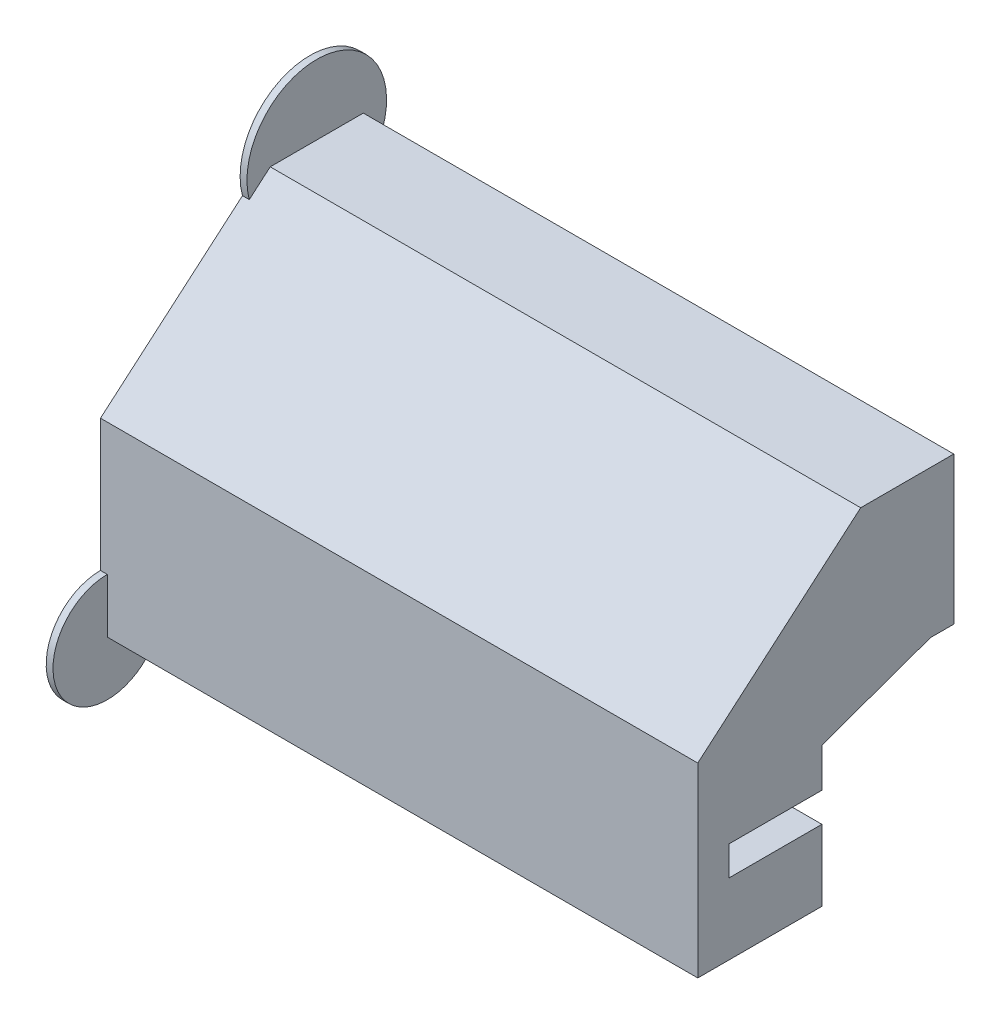
SolidWorks part; units mm, degrees
material "ABS"
ref_plane "Front Plane" through (0, 0, 0) normal (0, 0, 1) x (1, 0, 0)
ref_plane "Top Plane" through (0, 0, 0) normal (0, 1, 0) x (1, 0, 0)
ref_plane "Right Plane" through (0, 0, 0) normal (1, 0, 0) x (0, 0, -1)
sketch "Sketch1" plane through (0, 0, 0) normal (0, 0, 1) x (1, 0, 0)
  line L1 (-19.25, -10.5) -> (19.25, -10.5)
  line L2 (-19.25, -10.5) -> (-19.25, 10.5)
  line L3 (-19.25, 10.5) -> (19.25, 10.5)
  line L4 (19.25, -10.5) -> (19.25, 10.5)
  line L5 (-19.25, -10.5) -> (19.25, 10.5) construction
  line L6 (-19.25, 10.5) -> (19.25, -10.5) construction
  point P0 (0, 0)
  dimension "D1" = 38.5
  dimension "D2" = 21
extrude "Boss-Extrude1" add sketch "Sketch1" along normal blind 16.5 contours L3 L4 L1 L2
sketch "Sketch2" plane through (19.25, 0, 0) normal (1, 0, 0) x (0, 0, -1)
  line L0 (-16.5, -10.5) -> (-1.5, -10.5)
  line L2 (-1.5, -10.5) -> (-1.5, -6.5)
  line L3 (-1.5, -6.5) -> (0, -6.5)
  line L4 (0, -10.5) -> (0, 10.5) construction
  line L5 (0, -6.5) -> (0, 10.5)
  line L6 (0, 10.5) -> (-6, 10.5)
  line L8 (-6, 10.5) -> (-16.5, 1.5)
  line L9 (-16.5, -10.5) -> (-16.5, 10.5) construction
  line L10 (-16.5, 1.5) -> (-16.5, -10.5)
  line L11 (-8.5, -10.5) -> (-8.5, -1.5)
  line L12 (0, 1) -> (-1.5, 1)
  line L13 (-1.5, 1) -> (-8.5, -1.5)
  line L14 (-8.425, -3.1313) -> (-8.5, -3.1313)
  line L15 (-2.575, -6.5087) -> (-2.575, -3.1313)
  line L16 (-2.575, -3.1313) -> (-5.5, -1.4425)
  line L17 (-5.5, -1.4425) -> (-8.425, -3.1313)
  line L18 (-8.425, -3.1313) -> (-8.425, -6.5087)
  line L19 (-8.425, -6.5087) -> (-5.5, -8.1975)
  line L20 (-5.5, -8.1975) -> (-2.575, -6.5087)
  line L21 (-8.425, -6.5087) -> (-8.5, -6.5087)
  line L22 (-16.5, -10.5) -> (0, -10.5) construction
  line L23 (-6, 10.5) -> (-16.5, 10.5)
  line L24 (-16.5, 10.5) -> (-16.5, 1.5)
  line L25 (0, -10.5) -> (0, 10.5) construction
  line L26 (0, -6.5) -> (0, -10.5)
  line L27 (0, -10.5) -> (-1.5, -10.5)
  circle A0 centre (-5.5, -4.82) radius 1.7
  circle A1 centre (-5.5, -4.82) radius 2.925 construction
  line M1 (0, -10.5) -> (0, 10.5)
  line M3 (-16.5, 10.5) -> (-16.5, -10.5)
  line M42 (0, 10.5) -> (-16.5, 10.5)
  line M43 (-16.5, -10.5) -> (0, -10.5)
  dimension "D5" = 3.4
  dimension "D6" = 11
  dimension "D7" = 5.68
  dimension "D11" = 5.85
  dimension "D1" = 1.5
  dimension "D2" = 4
  dimension "D3" = 6
  dimension "D4" = 9
  dimension "D8" = 9
  dimension "D9" = 8
  dimension "D10" = 11.5
extrude "Cut-Extrude1" cut sketch "Sketch2" against normal up to surface (38.5 mm away) contours L8 M42 M3 | A0 region at (19.25, 7.5, 13) region at (19.25, -4.82, 5.5) up to face at (-19.25, 0, 8.25)
extrude "Cut-Extrude2" cut sketch "Sketch2<5>" against normal blind 14.5 contours L19 L21 L11 L0 L2 L3 L12 L13 L14 L17 L16 L15 L20 M1 | L19 L20 L15 L16 L17 L18 A0 | L21 L18 L14 L11 | L3 L2 M43 M1 region at (19.25, -8.5044, 8.357) region at (19.25, -8.5, 0.75) region at (19.25, -4.82, 8.4625) region at (19.25, -4.82, 8.3356)
sketch "Sketch2<5>" plane through (19.25, 0, 0) normal (1, 0, 0) x (0, 0, -1) same geometry as "Sketch2"
extrude "Cut-Extrude3" cut sketch "Sketch2<6>" against normal blind 2 from surface contours L19 L20 L15 L16 L17 L18 A0 | A0 | L21 L18 L14 L11 region at (19.25, -4.82, 8.4625) region at (19.25, -4.82, 8.3356) region at (19.25, -4.82, 5.5) starting at face at (4.75, -4.1, 3.7)
sketch "Sketch2<6>" plane through (19.25, 0, 0) normal (1, 0, 0) x (0, 0, -1) same geometry as "Sketch2"
sketch "Sketch3" plane through (-19.25, 0, 0) normal (-1, 0, 0) x (0, 0, 1)
  line L0 (2.1, -4.82) -> (15.1, -4.82) construction
  line L1 (13.1, -8.92) -> (4.1, -8.92)
  line L2 (15.1, -6.92) -> (15.1, -2.72)
  line L3 (13.1, -0.72) -> (4.1, -0.72)
  line L4 (2.1, -6.92) -> (2.1, -2.72)
  line L5 (15.1, -8.92) -> (2.1, -0.72) construction
  line L6 (15.1, -0.72) -> (2.1, -8.92) construction
  circle A0 centre (5.5, -4.82) radius 1.7 construction
  arc A1 (13.1, -0.72) -> (15.1, -2.72) centre (13.1, -2.72) cw
  arc A2 (15.1, -6.92) -> (13.1, -8.92) centre (13.1, -6.92) cw
  arc A3 (4.1, -8.92) -> (2.1, -6.92) centre (4.1, -6.92) cw
  arc A4 (2.1, -2.72) -> (4.1, -0.72) centre (4.1, -2.72) cw
  point P0 (8.6, -4.82)
  point P7 (5.5, -4.82)
  dimension "D4" = 2
  dimension "D1" = 13
  dimension "D2" = 8.2
  dimension "D3" = 3.4
extrude "Cut-Extrude4" cut sketch "Sketch3" against normal blind 18
sketch "Sketch4" plane through (0, 0, 0) normal (0, 0, -1) x (-1, 0, 0)
  line L0 (-19.25, 5) -> (19.1224, 5) construction
  line L1 (-19.25, 1) -> (-19.25, 10.5) construction
  line L2 (0, 0) -> (0, 10.5) construction
  line L3 (19.25, 10.5) -> (-19.25, 10.5) construction
  circle A0 centre (-6.75, 5) radius 1.3
  circle A1 centre (6.75, 5) radius 1.3
  dimension "D1" = 2.6
  dimension "D2" = 13.5
  dimension "D3" = 5.5
extrude "Cut-Extrude5" cut sketch "Sketch4" against normal blind 9.5
sketch "Sketch5" plane through (0, 0, 8.5) normal (0, 0, -1) x (-1, 0, 0)
  line L0 (-20.25, -5.92) -> (-4.75, -5.92)
  line L1 (-18.25, -4.72) -> (-18.25, -5.92) construction
  line L2 (-20.25, -5.92) -> (-18.25, -5.92) construction
  line L3 (-19.25, -4.02) -> (-19.25, -5.92) construction
  line L4 (-4.75, -10.5) -> (-4.75, -6.5087) construction
  line L5 (-4.75, -10.5) -> (-19.25, -10.5) construction
  line L6 (-18.05, -4.72) -> (-18.25, -4.72)
  line L7 (-17.6, -4.02) -> (-18.05, -4.72)
  line L8 (-17.6, -4.02) -> (-16.9, -4.02)
  line L9 (-16.45, -4.72) -> (-16.9, -4.02)
  line L10 (-16.25, -4.72) -> (-16.45, -4.72)
  line L11 (-16.05, -4.72) -> (-16.25, -4.72)
  line L12 (-15.6, -4.02) -> (-16.05, -4.72)
  line L13 (-15.6, -4.02) -> (-14.9, -4.02)
  line L14 (-14.45, -4.72) -> (-14.9, -4.02)
  line L15 (-14.25, -4.72) -> (-14.45, -4.72)
  line L16 (-14.05, -4.72) -> (-14.25, -4.72)
  line L17 (-13.6, -4.02) -> (-14.05, -4.72)
  line L18 (-13.6, -4.02) -> (-12.9, -4.02)
  line L19 (-12.45, -4.72) -> (-12.9, -4.02)
  line L20 (-12.25, -4.72) -> (-12.45, -4.72)
  line L21 (-12.05, -4.72) -> (-12.25, -4.72)
  line L22 (-11.6, -4.02) -> (-12.05, -4.72)
  line L23 (-11.6, -4.02) -> (-10.9, -4.02)
  line L24 (-10.45, -4.72) -> (-10.9, -4.02)
  line L25 (-10.25, -4.72) -> (-10.45, -4.72)
  line L26 (-10.05, -4.72) -> (-10.25, -4.72)
  line L27 (-9.6, -4.02) -> (-10.05, -4.72)
  line L28 (-18.25, -4.72) -> (-18.45, -4.72)
  line L29 (-18.45, -4.72) -> (-18.9, -4.02)
  line L30 (-9.6, -4.02) -> (-8.9, -4.02)
  line L31 (-19.6, -4.02) -> (-18.9, -4.02)
  line L32 (-19.6, -4.02) -> (-20.05, -4.72)
  line L33 (-20.05, -4.72) -> (-20.25, -4.72)
  line L34 (-8.45, -4.72) -> (-8.9, -4.02)
  line L35 (-20.25, -4.72) -> (-20.25, -5.92)
  line L36 (-8.25, -4.72) -> (-8.45, -4.72)
  line L37 (-8.05, -4.72) -> (-8.25, -4.72)
  line L38 (-7.6, -4.02) -> (-8.05, -4.72)
  line L39 (-7.6, -4.02) -> (-6.9, -4.02)
  line L40 (-6.45, -4.72) -> (-6.9, -4.02)
  line L41 (-6.25, -4.72) -> (-6.45, -4.72)
  line L42 (-6.05, -4.72) -> (-6.25, -4.72)
  line L43 (-5.6, -4.02) -> (-6.05, -4.72)
  line L44 (-5.6, -4.02) -> (-4.9, -4.02)
  line L45 (-4.75, -4.2534) -> (-4.9, -4.02)
  line L48 (-19.25, -10.5) -> (-19.25, -1.5) construction
  line L49 (-4.75, -5.92) -> (-4.75, -4.2534)
  line L52 (-4.25, -4.72) -> (-4.45, -4.72) [skipped]
  dimension "D1" = 2
  dimension "D2" = 0.7
  dimension "D3" = 1.2
  dimension "D4" = 4.58
  dimension "D5" = 0.7
  dimension "D6" = 0.2
  dimension "D7" = 8
  dimension "D8" = 2
extrude "Cut-Extrude7" cut sketch "Sketch5" against normal blind 6
chamfer "Chamfer3" distance 1 angle 45 2 edges at (-8.05, 5, 9.5) (5.45, 5, 9.5)
sketch "Sketch6" plane through (-19.25, 0, 0) normal (-1, 0, 0) x (0, 0, 1)
  line L0 (4.1, -0.72) -> (4.1, -8.92)
  line L1 (13.1, -0.72) -> (13.1, -8.92)
  line L2 (13, -10.5) -> (16.5, -10.5)
  line L3 (6, 10.5) -> (0, 10.5) construction
  line L4 (13.1, -0.72) -> (4.1, -0.72)
  line L5 (2.1, -2.72) -> (2.1, -6.92)
  line L6 (4.1, -8.92) -> (13.1, -8.92)
  line L7 (16.5, 1.5) -> (6, 10.5)
  line L8 (6, 10.5) -> (0, 10.5)
  line L9 (0, 10.5) -> (0, -10.5)
  line L10 (0, 10.5) -> (0, 7.1459)
  line L12 (0, -10.5) -> (16.5, -10.5)
  line L13 (16.5, -10.5) -> (16.5, 1.5)
  line L14 (0, 10.5) -> (6, 10.5)
  line L15 (6, 10.5) -> (7.3489, 9.3438)
  line L17 (0, -10.5) -> (0, 10.5) construction
  line L18 (6, 10.5) -> (16.5, 1.5) construction
  line L19 (0, -10.5) -> (3.5, -10.5)
  line L20 (16.5, -10.5) -> (16.5, -7)
  line L21 (15.1, -6.92) -> (15.1, -2.72)
  line L23 (2.1, -2.72) -> (2.1, -6.92)
  arc A0 (7.3489, 9.3438) -> (0, 7.1459) centre (3, 10.5) ccw
  arc A2 (0, -7) -> (3.5, -10.5) centre (0, -10.5) ccw
  arc A3 (13, -10.5) -> (16.5, -7) centre (16.5, -10.5) ccw
  arc A4 (15.1, -2.72) -> (13.1, -0.72) centre (13.1, -2.72) ccw
  arc A5 (4.1, -0.72) -> (2.1, -2.72) centre (4.1, -2.72) ccw
  arc A6 (2.1, -6.92) -> (4.1, -8.92) centre (4.1, -6.92) ccw
  arc A7 (13.1, -8.92) -> (15.1, -6.92) centre (13.1, -6.92) ccw
  arc A9 (4.1, -0.72) -> (2.1, -2.72) centre (4.1, -2.72) ccw
  arc A10 (2.1, -6.92) -> (4.1, -8.92) centre (4.1, -6.92) ccw
  arc A11 (13.1, -8.92) -> (15.1, -6.92) centre (13.1, -6.92) ccw
  arc M16 (13.1, -0.72) -> (15.1, -2.72) centre (13.1, -2.72) cw
  line M17 (15.1, -2.72) -> (15.1, -6.92)
  arc M18 (15.1, -6.92) -> (13.1, -8.92) centre (13.1, -6.92) cw
  arc M20 (4.1, -8.92) -> (2.1, -6.92) centre (4.1, -6.92) cw
  line M21 (2.1, -6.92) -> (2.1, -2.72)
  arc M22 (2.1, -2.72) -> (4.1, -0.72) centre (4.1, -2.72) cw
  line M24 (16.5, 1.5) -> (6, 10.5)
  line M26 (0, 10.5) -> (0, -10.5)
  line M29 (0, -10.5) -> (16.5, -10.5)
  line M30 (16.5, -10.5) -> (16.5, 1.5)
  dimension "D3" = 3.5
  dimension "D4" = 4.5
  dimension "D1" = 0
  dimension "D2" = 0
extrude "Boss-Extrude2" add sketch "Sketch6" against normal blind 0.44 contours M26 | M24 | A3 M29 M30 | L1 M16 M18 M17 | L0 M22 M21 M20 | A2 M29 region at (-19.25, -4.82, 3.1647) region at (-19.25, -4.82, 14.0353) region at (-19.25, -10.9951, 16.9951) region at (-19.25, -10.9951, -0.4951) region at (-19.25, 12.0446, 2.7507)
